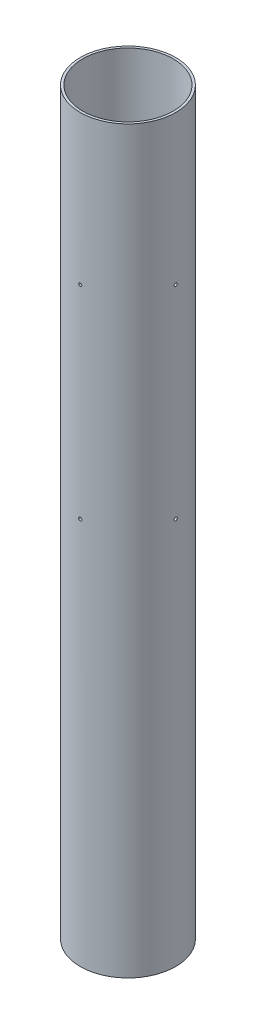
SolidWorks part; units mm, degrees
material "E-Glass Fiber"
ref_plane "Front Plane" through (0, 0, 0) normal (0, 0, 1) x (1, 0, 0)
ref_plane "Top Plane" through (0, 0, 0) normal (0, 1, 0) x (1, 0, 0)
ref_plane "Right Plane" through (0, 0, 0) normal (1, 0, 0) x (0, 0, -1)
sketch "Sketch1" plane through (0, 0, 0) normal (0, 1, 0) x (1, 0, 0)
  circle A0 centre (0, 0) radius 50.8
  dimension "D1" = 101.6
extrude "Coupler Extrusion" add sketch "Sketch1" along normal blind 787.4 thin thin type one direction reverse wall 2.54
ref_plane "Plane1" through (0, 0, 50.8) normal (0, 0, 1) x (1, 0, 0)
sketch "Sketch2" plane through (0, 0, 50.8) normal (0, 0, 1) x (1, 0, 0)
  line L0 (0, 787.4) -> (0, 0) construction
  line L1 (48.26, 787.4) -> (-48.26, 787.4) construction
  circle A0 centre (0, 628.65) radius 1.6383
  dimension "D1" = 3.2766
  dimension "D2" = 158.75
extrude "Bulkhead Hole" cut sketch "Sketch2" against normal up to next
pattern_circular "CirPattern1" count 4 over 360 about axis through (0, 787.4, 0) along (0, -1, 0) of "Bulkhead Hole"
sketch "Sketch3" plane through (0, 0, 50.8) normal (0, 0, 1) x (1, 0, 0)
  line L0 (0, 787.4) -> (0, 0) construction
  line L1 (50.8, 787.4) -> (-50.8, 787.4) construction
  line L2 (-48.26, 0) -> (48.26, 0) construction
  line L3 (-50.8, 0) -> (50.8, 0) construction
  line L4 (48.26, 787.4) -> (-48.26, 787.4) construction
  circle A0 centre (0, 412.75) radius 1.7526
  dimension "D1" = 3.5052
  dimension "D2" = 412.75
  dimension "D3" = 374.65
extrude "Lower Bulkhead Hole" cut sketch "Sketch3" against normal up to next
pattern_circular "CirPattern2" count 4 over 360 about axis through (0, 787.4, 0) along (0, -1, 0) of "Lower Bulkhead Hole" reverse direction yes
